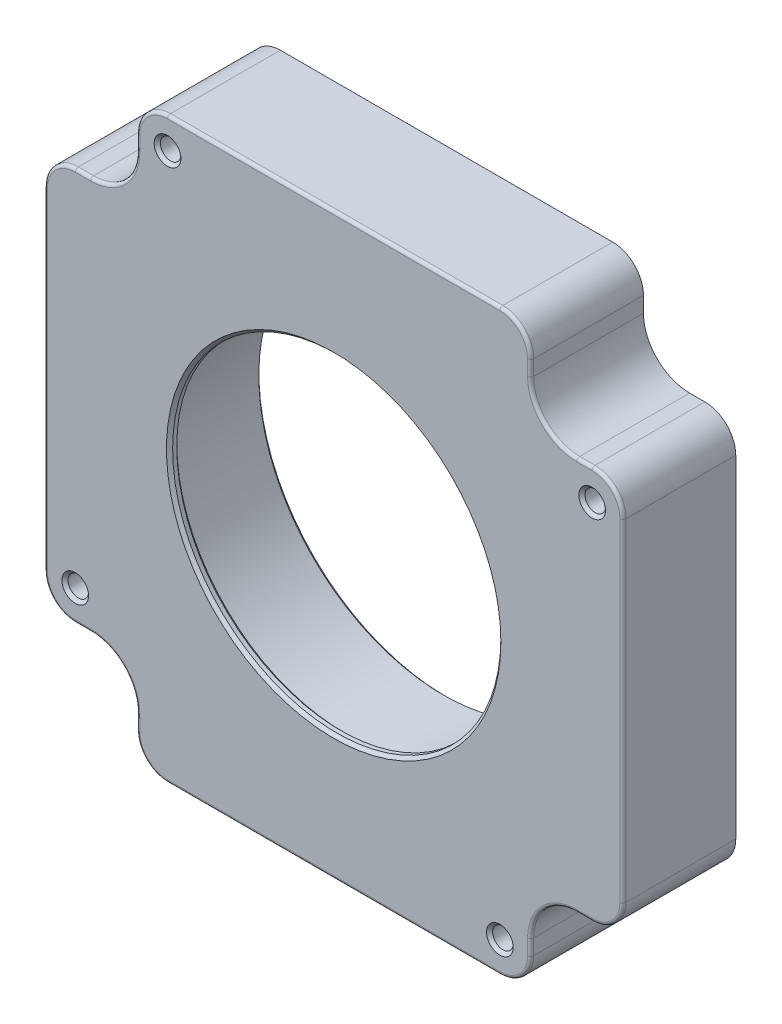
SolidWorks part; units mm, degrees
material "1060 Alloy"
ref_plane "Front Plane" through (0, 0, 0) normal (0, 0, 1) x (1, 0, 0)
ref_plane "Top Plane" through (0, 0, 0) normal (0, 1, 0) x (1, 0, 0)
ref_plane "Right Plane" through (0, 0, 0) normal (1, 0, 0) x (0, 0, -1)
sketch "Sketch1" plane through (0, 0, 0) normal (0, 0, 1) x (1, 0, 0)
  line L0 (0, 28.2) -> (0, -28.2) construction
  line L1 (-28.2, 28.2) -> (28.2, 28.2) construction
  line L2 (-28.2, 28.2) -> (-28.2, -28.2) construction
  line L3 (-28.2, -28.2) -> (28.2, -28.2) construction
  line L4 (28.2, 28.2) -> (28.2, -28.2) construction
  line L5 (-28.2, 28.2) -> (28.2, -28.2) construction
  line L6 (-28.2, -28.2) -> (28.2, 28.2) construction
  line L7 (-23.7, 23.7) -> (23.7, 23.7) construction
  line L8 (-23.7, 23.7) -> (-23.7, -23.7) construction
  line L9 (-23.7, -23.7) -> (23.7, -23.7) construction
  line L10 (23.7, 23.7) -> (23.7, -23.7) construction
  line L11 (-23.7, 23.7) -> (23.7, -23.7) construction
  line L12 (-23.7, -23.7) -> (23.7, 23.7) construction
  line L13 (-28.2, 0) -> (28.2, 0) construction
  line L14 (-23.7, 19.2) -> (-25.1852, 19.2)
  line L15 (-19.2, 23.7) -> (-19.2, 25.2)
  line L16 (16.2, -28.2) -> (-16.2, -28.2)
  line L17 (-28.2, -16.2) -> (-28.2, 16.2)
  line L18 (19.2, 23.7) -> (19.2, 25.2)
  line L19 (23.7, 19.2) -> (25.1852, 19.2)
  line L20 (28.2, 16.2) -> (28.2, -16.2)
  line L21 (16.2, 28.2) -> (-16.2, 28.2)
  line L23 (-23.7, -19.2) -> (-25.1852, -19.2)
  line L24 (-19.2, -23.7) -> (-19.2, -25.2)
  line L27 (23.7, -19.2) -> (25.1852, -19.2)
  line L28 (19.2, -23.7) -> (19.2, -25.2)
  circle A0 centre (0, 0) radius 16
  arc A1 (-16.2, 28.2) -> (-19.2, 25.2) centre (-16.2, 25.2) ccw
  arc A2 (-28.2, 16.2) -> (-25.1852, 19.2) centre (-25.2, 16.2) cw
  arc A3 (-23.7, 19.2) -> (-19.2, 23.7) centre (-23.7, 23.7) ccw
  arc A4 (23.7, 19.2) -> (19.2, 23.7) centre (23.7, 23.7) cw
  arc A5 (28.2, 16.2) -> (25.1852, 19.2) centre (25.2, 16.2) ccw
  circle A6 centre (-16.2, 25.2) radius 1
  arc A7 (16.2, 28.2) -> (19.2, 25.2) centre (16.2, 25.2) cw
  circle A8 centre (-25.2, -16.2) radius 1
  arc A9 (-28.2, -16.2) -> (-25.1852, -19.2) centre (-25.2, -16.2) ccw
  arc A10 (-23.7, -19.2) -> (-19.2, -23.7) centre (-23.7, -23.7) cw
  arc A11 (-16.2, -28.2) -> (-19.2, -25.2) centre (-16.2, -25.2) cw
  circle A12 centre (16.2, -25.2) radius 1
  arc A13 (28.2, -16.2) -> (25.1852, -19.2) centre (25.2, -16.2) cw
  arc A14 (23.7, -19.2) -> (19.2, -23.7) centre (23.7, -23.7) ccw
  arc A15 (16.2, -28.2) -> (19.2, -25.2) centre (16.2, -25.2) ccw
  circle A16 centre (25.2, 16.2) radius 1
  point P0 (0, 0)
  point P6 (0, 0)
  dimension "D3" = 32
  dimension "D1" = 56.4
  dimension "D2" = 47.4
extrude "Boss-Extrude1" add sketch "Sketch1" along normal blind 11
sketch "Sketch2" plane through (0, 0, 0) normal (0, 0, 1) x (1, 0, 0)
  line L0 (-16.2, -28.2) -> (16.2, -28.2) construction
  line L1 (-10.811, -26.1) -> (10.811, -26.1)
  line L2 (10.811, -26.1) -> (26.1, -10.811)
  line L3 (26.1, -10.811) -> (26.1, 10.811)
  line L4 (26.1, 10.811) -> (10.811, 26.1)
  line L5 (10.811, 26.1) -> (-10.811, 26.1)
  line L6 (-10.811, 26.1) -> (-26.1, 10.811)
  line L7 (-26.1, 10.811) -> (-26.1, -10.811)
  line L8 (-26.1, -10.811) -> (-10.811, -26.1)
  circle A0 centre (0, 0) radius 26.1 construction
  circle A1 centre (0, 0) radius 20
  dimension "D1" = 52.2
  dimension "D2" = 40
extrude "Cut-Extrude1" cut sketch "Sketch2" along normal blind 8.5
sketch "Sketch3" plane through (0, 0, 0) normal (0, 0, -1) x (-1, 0, 0)
  circle A0 centre (0, 0) radius 16
  circle A1 centre (0, 0) radius 18
  dimension "D1" = 36
extrude "Cut-Extrude2" cut sketch "Sketch3" against normal blind 10
fillet "Fillet1" radius 0.3 24 edges at (27.3161, -18.3266, 11) (24.4426, -19.2, 11) (20.518, -20.518, 11) (19.2, -24.45, 11) (18.3213, -27.3213, 11) (0, -28.2, 11) (-18.3213, -27.3213, 11) (-19.2, -24.45, 11) (-20.518, -20.518, 11) (-24.4426, -19.2, 11) (-27.3161, -18.3266, 11) (-28.2, 0, 11) (-27.3161, 18.3266, 11) (-24.4426, 19.2, 11) (-20.518, 20.518, 11) (-19.2, 24.45, 11) (-18.3213, 27.3213, 11) (0, 28.2, 11) (18.3213, 27.3213, 11) (19.2, 24.45, 11) (20.518, 20.518, 11) (24.4426, 19.2, 11) (27.3161, 18.3266, 11) (28.2, 0, 11)
chamfer "Chamfer1" distance 0.3 angle 45 20 edges at (15.2, -25.2, 11) (-26.2, -16.2, 11) (-17.2, 25.2, 11) (24.2, 16.2, 11) (16, 0, 11) (-16, 0, 10) (20, 0, 0) (-18, 0, 0) (-18.4555, -18.4555, 0) (0, -26.1, 0) (18.4555, -18.4555, 0) (26.1, 0, 0) (18.4555, 18.4555, 0) (0, 26.1, 0) (-26.1, 0, 0) (-18.4555, 18.4555, 0) (-26.2, -16.2, 0) (15.2, -25.2, 0) (24.2, 16.2, 0) (-17.2, 25.2, 0)
sketch "Sketch4" plane through (-28.2, 0, 0) normal (-1, 0, 0) x (0, 0, 1)
  line L0 (0, 0) -> (11, 0) construction
  line L1 (11, 16.2) -> (11, -16.2) construction
  line L2 (0, 16.2) -> (0, -16.2) construction
  line L3 (5.5, 4) -> (0, 4) construction
  line L4 (5.5, 4) -> (5.5, -4) construction
  line L5 (5.5, -4) -> (0, -4) construction
  line L6 (0, 4) -> (0, -4) construction
  line L8 (0, 4) -> (5.5, 4)
  line L9 (0, 4) -> (0, -4)
  line L10 (0, -4) -> (5.5, -4)
  circle A0 centre (5.5, 0) radius 4 construction
  arc A1 (5.5, -4) -> (5.5, 4) centre (5.5, 0) ccw
  dimension "D1" = 8
extrude "Cut-Extrude3" cut sketch "Sketch4" against normal up to vertex (2.1 mm away) up to point (-26.1, 10.811, 0.3)
sketch "Sketch5" plane through (0, 0, 0) normal (0, 0, -1) x (-1, 0, 0)
  line L0 (0, 0) -> (28.2, 0) construction
  line L1 (28.2, -4) -> (28.2, 4) construction
  line L3 (27, 6) -> (24, 6)
  line L4 (27, 6) -> (27, -6)
  line L5 (27, -6) -> (24, -6)
  line L6 (24, 6) -> (24, -6)
  point P9 (27, 0)
  dimension "D1" = 12
  dimension "D2" = 3
  dimension "D3" = 27
extrude "Cut-Extrude5" cut sketch "Sketch5" against normal blind 10
